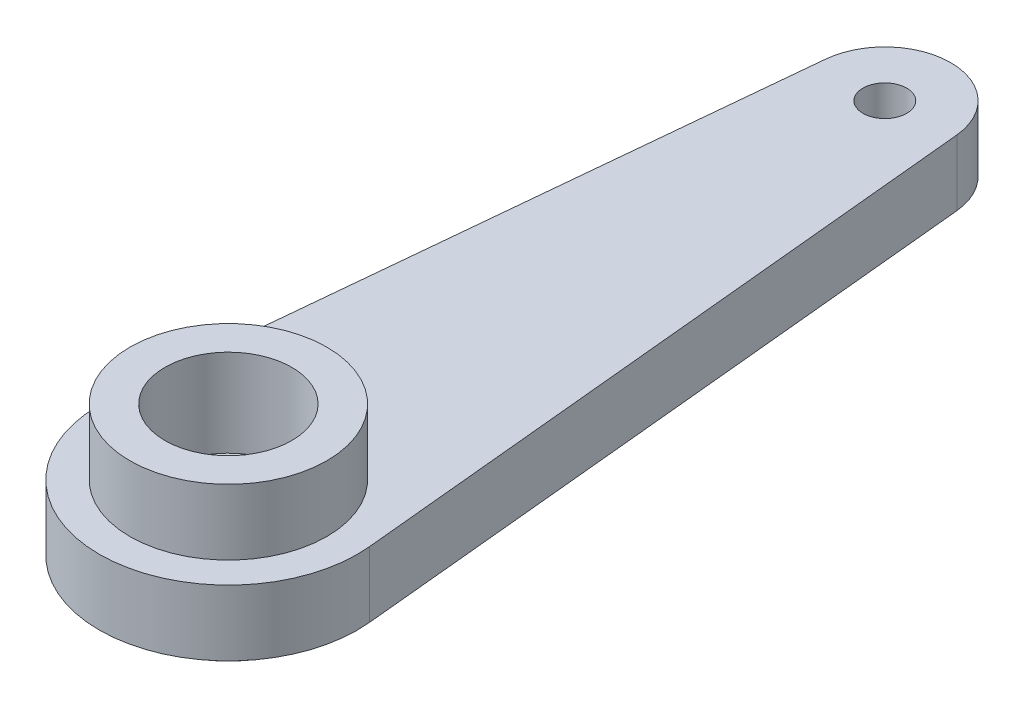
SolidWorks part; units mm, degrees
ref_plane "Front Plane" through (0, 0, 0) normal (0, 0, 1) x (1, 0, 0)
ref_plane "Top Plane" through (0, 0, 0) normal (0, 1, 0) x (1, 0, 0)
ref_plane "Right Plane" through (0, 0, 0) normal (1, 0, 0) x (0, 0, -1)
sketch "Sketch2" plane through (0, 0, 0) normal (0, 1, 0) x (1, 0, 0)
  line L2 (0, 0) -> (0, 30) construction
  line L3 (-3, 30.2899) -> (-5.8726, 0.5676)
  line L4 (3, 30.2899) -> (5.8726, 0.5676)
  circle A0 centre (0, 0) radius 1.25
  circle A1 centre (0, 30) radius 1
  arc A2 (-3, 30.2899) -> (3, 30.2899) centre (0, 30) cw
  arc A3 (-5.8726, 0.5676) -> (5.8726, 0.5676) centre (0, 0) ccw
  circle A4 centre (0, 0) radius 2.9
  dimension "D1" = 2.5
  dimension "D2" = 2
  dimension "D6" = 5.8
  dimension "D5" = 3
  dimension "D3" = 30
  dimension "D4" = 3
extrude "Boss-Extrude1" add sketch "Sketch2" along normal blind 3 contours L3 A3 L4 A2 A4 A1 | L3 A3 L4 A2 | A1 | A4 region at (0, 0, -12.3693)
extrude "Boss-Extrude2" add sketch "Sketch2<4>" along normal blind 2 contours A0 A4 region at (-2.818, 0, 0)
sketch "Sketch2<4>" plane through (0, 0, 0) normal (0, 1, 0) x (1, 0, 0) same geometry as "Sketch2"
sketch "Sketch6" plane through (0, 0, 0) normal (0, 1, 0) x (1, 0, 0)
  line L0 (0, 0) -> (0, 30) construction
ref_axis "Axis1" through (0, 0, 0) along (0, 0, -1)
sketch "Sketch7" plane through (0, 3, 0) normal (0, 1, 0) x (1, 0, 0)
  circle A0 centre (0, 0) radius 4.5
  circle A1 centre (0, 0) radius 2.9
  dimension "D1" = 9
  dimension "D2" = 5.8
extrude "Boss-Extrude3" add sketch "Sketch7" along normal blind 3
sketch "Sketch8" plane through (0, 0, 0) normal (0, -1, 0) x (1, 0, 0)
  circle A0 centre (0, 0) radius 2.875
  circle A1 centre (0, 0) radius 4.5
  dimension "D1" = 5.75
  dimension "D2" = 9
extrude "Boss-Extrude4" add sketch "Sketch8" along normal blind 1
sketch "Sketch9" plane through (0, 0, 0) normal (0, -1, 0) x (1, 0, 0)
  circle A0 centre (0, 0) radius 2.875
  dimension "D1" = 5.75
extrude "Cut-Extrude2" cut sketch "Sketch9" against normal blind 0.5
